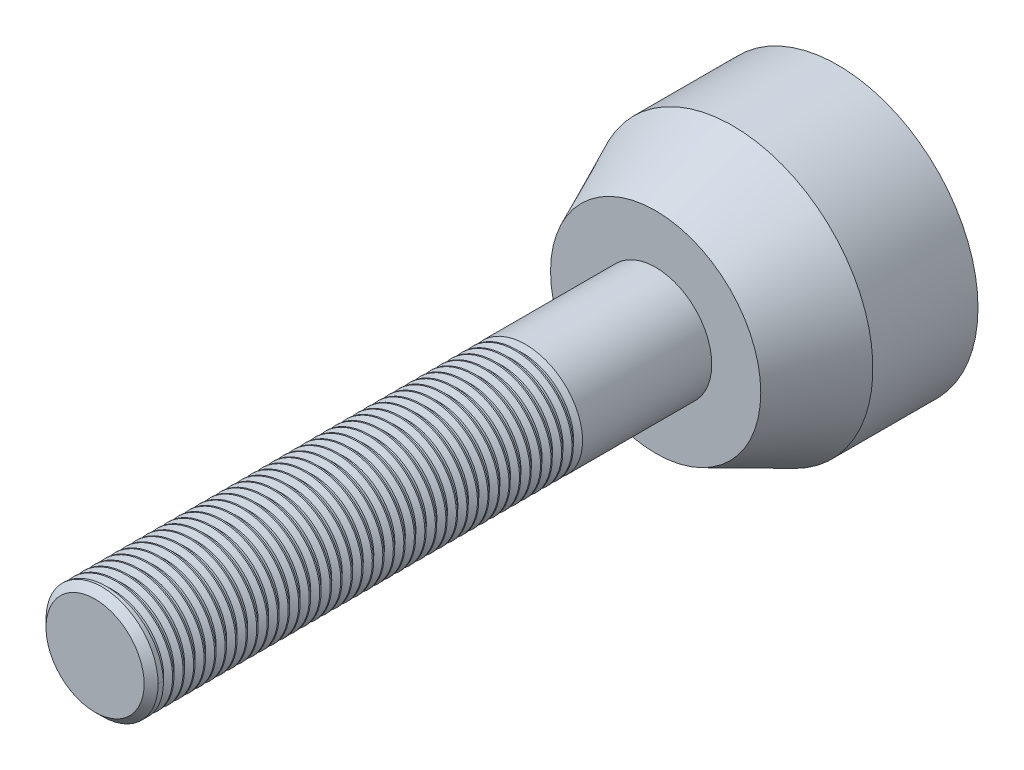
SolidWorks part; units mm, degrees
ref_plane "前视基准面" through (0, 0, 0) normal (0, 0, 1) x (1, 0, 0)
ref_plane "上视基准面" through (0, 0, 0) normal (0, 1, 0) x (1, 0, 0)
ref_plane "右视基准面" through (0, 0, 0) normal (1, 0, 0) x (0, 0, -1)
sketch "草图1" plane through (0, 0, 0) normal (0, 0, 1) x (1, 0, 0)
  circle A0 centre (0, 0) radius 20
  dimension "D1" = 40
extrude "凸台-拉伸1" add sketch "草图1" along normal blind 106
sketch "草图3" plane through (0, 0, 106) normal (0, 0, 1) x (1, 0, 0)
  circle A0 centre (0, 0) radius 8
  circle A1 centre (0, 0) radius 29.7459
extrude "切除-拉伸2" cut sketch "草图3" against normal blind 80
sketch "草图4" plane through (0, 0, 0) normal (0, 1, 0) x (1, 0, 0)
  line L0 (15, -26) -> (20, -15)
  line L1 (-20, -26) -> (20, -26) construction
  line L2 (20, -26) -> (20, 0) construction
  line L3 (15, -26) -> (20, -26)
  line L4 (20, -26) -> (20, -15)
  line L5 (20, -26) -> (20, -15)
  line L6 (0, 0) -> (0, -106) construction
  line L7 (20, 0) -> (-20, 0) construction
  line L8 (-8, -106) -> (8, -106) construction
  line L9 (0, -106) -> (0, -109.8862) construction
  point P14 (0, 0)
  dimension "D1" = 5
  dimension "D2" = 11
revolve "切除-旋转1" cut sketch "草图4" angle 360 about L6 region at (18.3333, 0, 22.3333)
fillet "倒角5" radius 1 1 edges at (8, 0, 106) type face fillet profile chamfer first side face at (8, 0, 26) second side face at (8, 0, 106)
thread "螺纹线1" pitch 1.5 method cut profile "螺纹线轮廓1" start angle 0, offset 0, length 60, pitch 1.5, diameter 16
ref_plane "基准面1" through (-8, 0, 105) normal (0, -1, 0) x (-1, 0, 0)
sketch "螺纹线轮廓1" plane through (-8, 0, 105) normal (0, -1, 0) x (-1, 0, 0)
  line L0 (0, 0) -> (0, 1.5) construction
  line L11 (0, 0) -> (0, 1.3125)
  line L12 (0, 1.3125) -> (-0.8119, 0.8437)
  line L13 (-0.8119, 0.8437) -> (-0.8119, 0.4687)
  line L15 (-0.8119, 0.4687) -> (0, 0)
  line L17 (-0.8119, 0.6562) -> (0, 0.6562) construction
  point P2 (0, 0)
  dimension "Pitch" = 1.5
  dimension "Profile_Angle" = 60
  dimension "Profile_Land" = 0.375
  dimension "Profile_Height" = 0.8119
